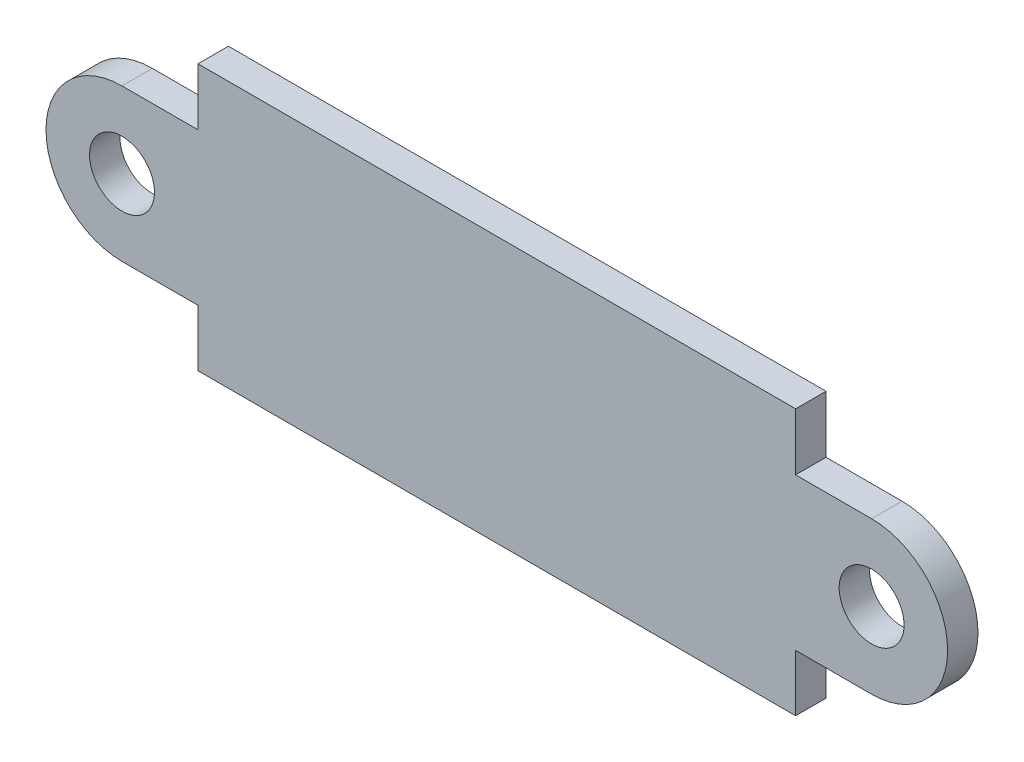
SolidWorks part; units mm, degrees
ref_plane "Front Plane" through (0, 0, 0) normal (0, 0, 1) x (1, 0, 0)
ref_plane "Top Plane" through (0, 0, 0) normal (0, 1, 0) x (1, 0, 0)
ref_plane "Right Plane" through (0, 0, 0) normal (1, 0, 0) x (0, 0, -1)
sketch "Sketch1" plane through (0, 0, 0) normal (0, 0, 1) x (1, 0, 0)
  line L0 (-3.7465, -6.5659) -> (33.2105, -6.5659) construction
  line L1 (0, 0) -> (29.464, 0)
  line L2 (0, 0) -> (0, -2.8194)
  line L3 (0, -13.1064) -> (29.464, -13.1064)
  line L4 (29.464, 0) -> (29.464, -2.8194)
  line L5 (0, 0) -> (29.464, -13.1064) construction
  line L6 (0, -13.1064) -> (29.464, 0) construction
  line L7 (-3.7465, -2.8194) -> (0, -2.8194)
  line L8 (-3.7465, -10.3124) -> (0, -10.3124)
  line L9 (29.464, -2.8194) -> (33.2105, -2.8194)
  line L10 (29.464, -10.3124) -> (33.2105, -10.3124)
  line L11 (0, -10.3124) -> (0, -13.1064)
  line L12 (29.464, -10.3124) -> (29.464, -13.1064)
  arc A0 (-3.7465, -2.8194) -> (-3.7465, -10.3124) centre (-3.7465, -6.5659) ccw
  arc A1 (33.2105, -10.3124) -> (33.2105, -2.8194) centre (33.2105, -6.5659) ccw
  circle A2 centre (-3.7465, -6.5659) radius 1.6002
  circle A3 centre (33.2105, -6.5659) radius 1.6002
  point P4 (14.732, -6.5532)
  point P8 (14.732, -6.5659)
  dimension "D3" = 36.957
  dimension "D6" = 3.2004
  dimension "D7" = 3.2004
  dimension "D1" = 29.464
  dimension "D2" = 13.1064
  dimension "D4" = 7.493
  dimension "D5" = 2.8194
extrude "Boss-Extrude1" add sketch "Sketch1" against normal blind 1.4986
